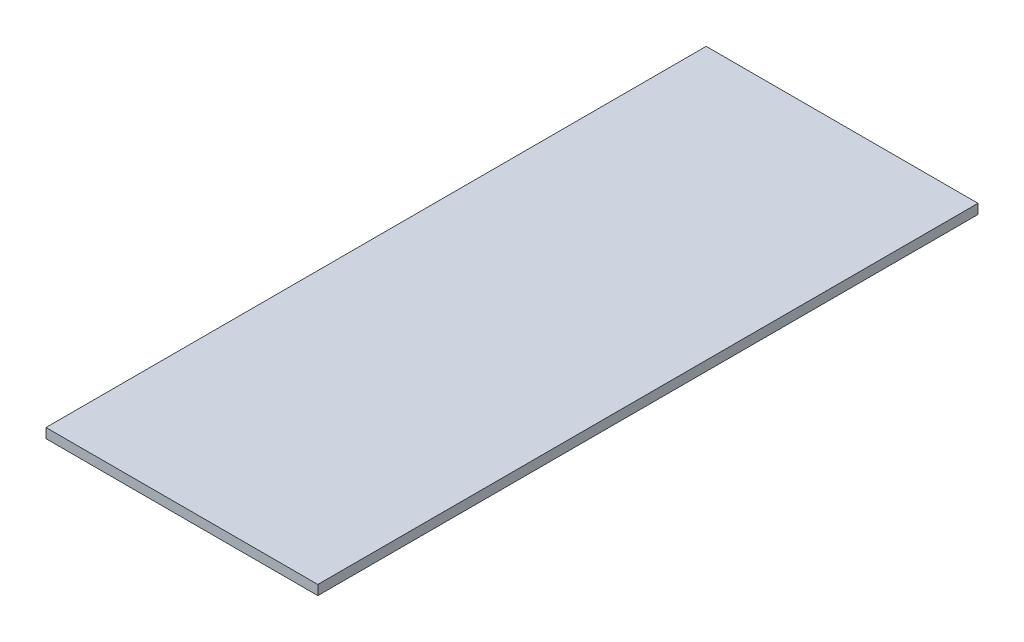
SolidWorks part; units mm, degrees
ref_plane "Front Plane" through (0, 0, 0) normal (0, 0, 1) x (1, 0, 0)
ref_plane "Top Plane" through (0, 0, 0) normal (0, 1, 0) x (1, 0, 0)
ref_plane "Right Plane" through (0, 0, 0) normal (1, 0, 0) x (0, 0, -1)
sketch "Sketch1" plane through (0, 0, 0) normal (0, 1, 0) x (1, 0, 0)
  line L1 (-70, -170) -> (70, -170)
  line L2 (-70, -170) -> (-70, 170)
  line L3 (-70, 170) -> (70, 170)
  line L4 (70, -170) -> (70, 170)
  line L5 (-70, -170) -> (70, 170) construction
  line L6 (-70, 170) -> (70, -170) construction
  point P0 (0, 0)
  dimension "D1" = 140
  dimension "D2" = 340
extrude "Boss-Extrude1" add sketch "Sketch1" along normal blind 5
sketch "Sketch2" plane through (0, 5, 0) normal (0, 1, 0) x (1, 0, 0)
  line L3 (70, 170) -> (-70, 170) construction
  line L7 (-70, -170) -> (70, -170) construction
  line L8 (-12.05, 170) -> (-12.05, -170)
  line L9 (12.05, 170) -> (12.05, -170)
